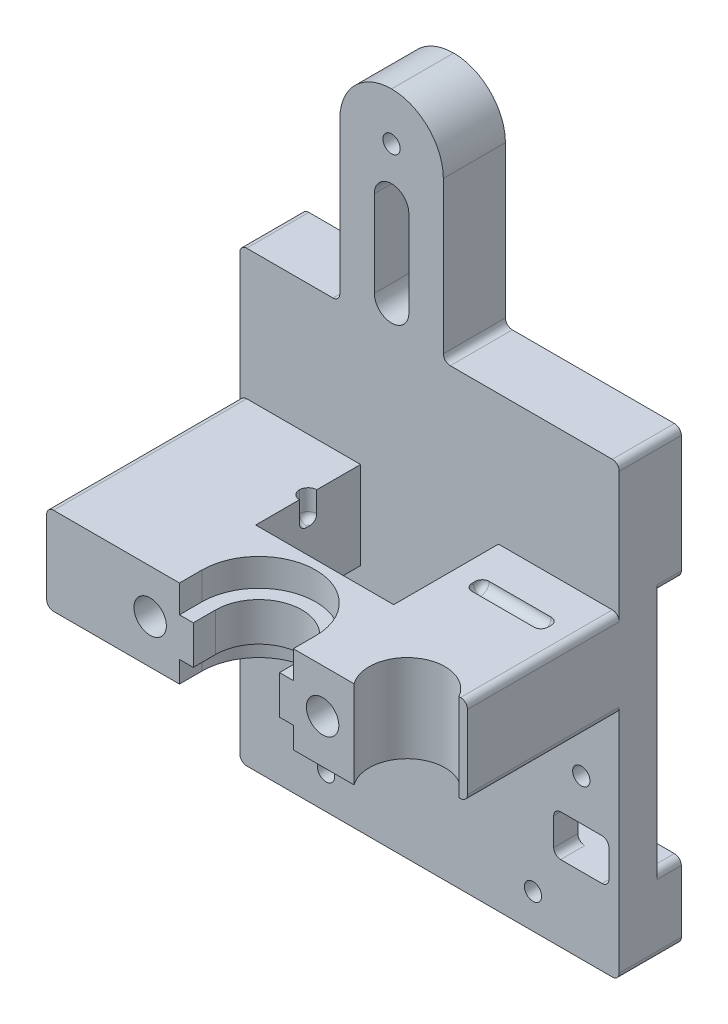
SolidWorks part; units mm, degrees
ref_plane "XY" through (0, 0, 0) normal (0, 0, 1) x (1, 0, 0)
ref_plane "XZ" through (0, 0, 0) normal (0, 1, 0) x (1, 0, 0)
ref_plane "YZ" through (0, 0, 0) normal (1, 0, 0) x (0, 0, -1)
sketch "Sketch1" plane through (0, 0, 0) normal (0, 0, 1) x (1, 0, 0)
  line L0 (-27.5, 17.25) -> (-13, 17.25)
  line L1 (27.5, 47.75) -> (2, 47.75) construction
  line L2 (27.5, 47.75) -> (27.5, 17.25) construction
  line L3 (27.5, -47.75) -> (-27.5, -47.75)
  line L4 (-27.5, 47.75) -> (-27.5, 17.25) construction
  line L5 (27.5, 47.75) -> (-27.5, -47.75) construction
  line L6 (27.5, -47.75) -> (-27.5, 47.75) construction
  line L7 (-13, 17.25) -> (-13, 47.75)
  line L8 (2, 47.75) -> (2, 17.25)
  line L9 (2, 17.25) -> (27.5, 17.25)
  line L10 (-27.5, 17.25) -> (-27.5, -47.75)
  line L11 (-13, 47.75) -> (-27.5, 47.75) construction
  line L12 (2, 47.75) -> (-13, 47.75)
  line L13 (27.5, 17.25) -> (27.5, -47.75)
  line L14 (-5.5, 33.35) -> (-5.5, 20.85) construction
  line L15 (-3, 33.35) -> (-3, 20.85)
  line L16 (-8, 33.35) -> (-8, 20.85)
  line L17 (0, 0) -> (0, -86.6792) construction
  line L18 (26, -30.75) -> (18, -30.75)
  line L19 (26, -30.75) -> (26, -36.75)
  line L20 (26, -36.75) -> (18, -36.75)
  line L21 (18, -30.75) -> (18, -36.75)
  line L22 (26, -30.75) -> (18, -36.75) construction
  line L23 (26, -36.75) -> (18, -30.75) construction
  arc A0 (-3, 33.35) -> (-8, 33.35) centre (-5.5, 33.35) ccw
  arc A1 (-8, 20.85) -> (-3, 20.85) centre (-5.5, 20.85) ccw
  circle A2 centre (-5.5, 40.85) radius 1.25
  circle A3 centre (-22, -24.75) radius 1.25
  circle A4 centre (-15, -42.75) radius 1.25
  circle A5 centre (15, -42.75) radius 1.25
  circle A6 centre (22, -24.75) radius 1.25
  point P0 (0, 0)
  point P14 (-5.5, 27.1)
  point P21 (22, -33.75)
  dimension "D6" = 2.5
  dimension "D10" = 2.5
  dimension "D16" = 2.5
  dimension "D1" = 55
  dimension "D2" = 95.5
  dimension "D3" = 14.5
  dimension "D4" = 25.5
  dimension "D5" = 30.5
  dimension "D7" = 12.5
  dimension "D8" = 7.5
  dimension "D9" = 20.65
  dimension "D11" = 6.9
  dimension "D12" = 8
  dimension "D13" = 6
  dimension "D14" = 5.5
  dimension "D15" = 14
  dimension "D17" = 5.5
  dimension "D18" = 12.5
  dimension "D19" = 5
  dimension "D20" = 23
extrude "Boss-Extrude1" add sketch "Sketch1" along normal blind 9
fillet "Fillet1" radius 7.5 2 edges at (-13, 47.75, 4.5) (2, 47.75, 4.5)
fillet "Fillet2" radius 1 6 edges at (-27.5, -47.75, 4.5) (-13, 17.25, 4.5) (-27.5, 17.25, 4.5) (2, 17.25, 4.5) (27.5, 17.25, 4.5) (27.5, -47.75, 4.5)
ref_plane "Plane1" through (0, -14.35, 0) normal (0, -1, 0) x (-1, 0, 0)
sketch "Sketch2" plane through (0, -14.35, 0) normal (0, -1, 0) x (-1, 0, 0)
  line L0 (-27.5, 0) -> (-27.5, -9) construction
  line L1 (27.5, -9) -> (10, -9)
  line L2 (27.5, -9) -> (27.5, -37)
  line L3 (27.5, -37) -> (6.25, -37)
  line L4 (-27.5, -9) -> (-27.5, -31)
  line L5 (-10, -9) -> (-27.5, -9)
  line L6 (-10, -24.2) -> (10, -24.2)
  line L7 (-10, -24.2) -> (-10, -9)
  line L8 (-27.5, -31) -> (-26.2631, -31)
  line L9 (10, -24.2) -> (10, -9)
  line L10 (-10, -24.2) -> (10, -9) construction
  line L11 (-10, -9) -> (10, -24.2) construction
  line L12 (-17.0629, -37) -> (-27.5, -37) construction
  line L13 (-27.5, -31) -> (-27.5, -37) construction
  line L14 (6.25, -33.75) -> (6.25, -37)
  line L15 (-6.25, -33.75) -> (-6.25, -37)
  line L16 (-6.25, -37) -> (-17.0629, -37)
  arc A0 (-26.2631, -31) -> (-17.0629, -37) centre (-21.5, -33.75) cw
  arc A1 (6.25, -33.75) -> (-6.25, -33.75) centre (0, -33.75) ccw
  point P7 (0, -16.6)
  dimension "D4" = 5.5
  dimension "D8" = 12.5
  dimension "D1" = 28
  dimension "D2" = 20
  dimension "D3" = 15.2
  dimension "D5" = 6
  dimension "D6" = 6
  dimension "D7" = 3.25
  dimension "D9" = 3.25
extrude "Boss-Extrude2" add sketch "Sketch2" against normal blind 12.7
sketch "Sketch3" plane through (0, 0, 37) normal (0, 0, 1) x (1, 0, 0)
  line L0 (-6.25, -1.65) -> (-8.25, -1.65)
  line L1 (-27.5, -1.65) -> (-10, -1.65) construction
  line L2 (-8.25, -1.65) -> (-8.25, -5.65)
  line L3 (-8.25, -5.65) -> (-6.25, -5.65)
  line L4 (-6.25, -1.65) -> (-6.25, -14.35) construction
  line L5 (-6.25, -5.65) -> (-6.25, -1.65)
  line L6 (-6.25, -14.35) -> (-6.25, -11.25)
  line L7 (-28.6032, -14.35) -> (28.6032, -14.35) construction
  line L8 (-6.25, -11.25) -> (-8.25, -11.25)
  line L9 (-8.25, -11.25) -> (-8.25, -14.35)
  line L10 (-8.25, -14.35) -> (-6.25, -14.35)
  line L11 (-27.5, -8) -> (8.666, -8) construction
  line L12 (-27.5, -1.65) -> (-27.5, -14.35) construction
  dimension "D1" = 4
  dimension "D2" = 2
  dimension "D3" = 3.1
sketch "Sketch4" plane through (0, -1.65, 0) normal (0, 1, 0) x (1, 0, 0)
  line L0 (-6.25, -33.75) -> (-6.25, -37) construction
  line L1 (6.25, -37) -> (6.25, -33.75) construction
  line L2 (-6.25, -33.75) -> (-6.25, -37)
  line L3 (6.25, -37) -> (6.25, -33.75)
  arc A0 (6.25, -33.75) -> (-6.25, -33.75) centre (0, -33.75) ccw construction
  arc A1 (6.25, -33.75) -> (-6.25, -33.75) centre (0, -33.75) ccw
sweep "Cut-Sweep1" cut profiles "Sketch3" path "Sketch4"
sketch "Sketch5" plane through (0, 0, 37) normal (0, 0, 1) x (1, 0, 0)
  line L0 (0, 0) -> (0, -23.2005) construction
  circle A0 centre (-12.5, -8) radius 1.75
  circle A1 centre (12.5, -8) radius 1.75
  dimension "D1" = 12.5
  dimension "D3" = 3.5
  dimension "D2" = 8
extrude "Cut-Extrude1" cut sketch "Sketch5" against normal blind 10
sketch "Sketch6" plane through (0, 0, 37) normal (0, 0, 1) x (1, 0, 0)
  circle A0 centre (-12.5, -8) radius 2.35
  circle A1 centre (12.5, -8) radius 2.35
  dimension "D1" = 4.7
extrude "Cut-Extrude2" cut sketch "Sketch6" against normal blind 5
sketch "Sketch7" plane through (-10, 0, 0) normal (1, 0, 0) x (0, 0, -1)
  line L0 (-9, -1.65) -> (-24.2, -1.65) construction
  line L1 (-17.85, -1.65) -> (-15.35, -1.65)
  line L2 (-17.85, -1.65) -> (-17.85, -5.65)
  line L3 (-17.85, -5.65) -> (-15.35, -5.65)
  line L4 (-15.35, -1.65) -> (-15.35, -5.65)
  dimension "D1" = 2.5
  dimension "D2" = 4
  dimension "D3" = 15.35
extrude "Cut-Extrude3" cut sketch "Sketch7" against normal blind 1.25
fillet "Fillet3" radius 1.25 2 edges at (-11.25, -3.65, 17.85) (-11.25, -3.65, 15.35)
fillet "Fillet4" radius 1 2 edges at (-10.8839, -5.65, 15.7161) (-10.8839, -5.65, 17.4839)
sketch "Sketch8" plane through (0, -1.65, 0) normal (0, 1, 0) x (1, 0, 0)
  line L1 (13, -14.35) -> (24, -14.35)
  line L2 (13, -14.35) -> (13, -16.85)
  line L3 (13, -16.85) -> (24, -16.85)
  line L4 (24, -14.35) -> (24, -16.85)
  dimension "D1" = 11
  dimension "D2" = 2.5
  dimension "D3" = 14.35
  dimension "D4" = 13
extrude "Cut-Extrude4" cut sketch "Sketch8" against normal blind 1.25
fillet "Fillet5" radius 1.25 2 edges at (18.5, -2.9, 16.85) (18.5, -2.9, 14.35)
fillet "Fillet6" radius 1 4 edges at (24, -2.5339, 16.4839) (13, -2.5339, 16.4839) (24, -2.5339, 14.7161) (13, -2.5339, 14.7161)
sketch "Sketch9" plane through (0, 0, 0) normal (0, 0, -1) x (-1, 0, 0)
  line L0 (0, 0) -> (0, -62.4758) construction
  circle A0 centre (0, -15.25) radius 2.35
  circle A1 centre (-12, -3.25) radius 1.5
  circle A2 centre (-12, -27.25) radius 1.5
  circle A3 centre (-22, -5.75) radius 1.25
  circle A4 centre (12, -27.25) radius 1.5
  circle A5 centre (12, -3.25) radius 1.5
  circle A6 centre (22, -5.75) radius 1.25
  dimension "D1" = 4.7
  dimension "D3" = 12
  dimension "D5" = 3
  dimension "D9" = 2.5
  dimension "D2" = 15.25
  dimension "D4" = 3.25
  dimension "D6" = 24
  dimension "D7" = 10
  dimension "D8" = 2.5
extrude "Cut-Extrude5" cut sketch "Sketch9" against normal blind 8 contours A1 | A2 | A5 | A4
extrude "Cut-Extrude6" cut sketch "Sketch9<3>" against normal blind 5 contours A0
sketch "Sketch9<3>" plane through (0, 0, 0) normal (0, 0, -1) x (-1, 0, 0) same geometry as "Sketch9"
extrude "Cut-Extrude7" cut sketch "Sketch9<4>" against normal blind 23 contours A3 | A6
sketch "Sketch9<4>" plane through (0, 0, 0) normal (0, 0, -1) x (-1, 0, 0) same geometry as "Sketch9"
sketch "Sketch10" plane through (0, 0, 0) normal (0, 0, -1) x (-1, 0, 0)
  circle A0 centre (0, -15.25) radius 1.5
  dimension "D1" = 3
extrude "Cut-Extrude8" cut sketch "Sketch10" against normal blind 8
sketch "Sketch11" plane through (0, 0, 0) normal (0, 0, -1) x (-1, 0, 0)
  line L0 (-27.5, -46.75) -> (-27.5, 16.25) construction
  line L1 (-27.5, -1.75) -> (-16.5, -1.75)
  line L2 (-27.5, -1.75) -> (-27.5, -36.75)
  line L3 (-27.5, -36.75) -> (-16.5, -36.75)
  line L4 (-16.5, -1.75) -> (-16.5, -36.75)
  dimension "D1" = 35
  dimension "D2" = 11
  dimension "D3" = 1.75
extrude "Cut-Extrude9" cut sketch "Sketch11" against normal blind 3.5
sketch "Sketch13" plane through (0, 0, 3.5) normal (0, 0, -1) x (-1, 0, 0)
  line L0 (-16.5, -36.75) -> (-16.5, -1.75) construction
  line L1 (-17.3, -9.25) -> (-26.7, -9.25)
  line L2 (-17.3, -9.25) -> (-17.3, -21.25)
  line L3 (-17.3, -21.25) -> (-26.7, -21.25)
  line L4 (-26.7, -9.25) -> (-26.7, -21.25)
  line L5 (-16.5, -1.75) -> (-27.5, -1.75) construction
  dimension "D1" = 0.8
  dimension "D2" = 9.4
  dimension "D3" = 12
  dimension "D4" = 7.5
extrude "Cut-Extrude10" cut sketch "Sketch13" against normal blind 1.5
mirror "Mirror1" about plane through (0, 0, 0) normal (1, 0, 0) of "Cut-Extrude10", "Cut-Extrude9"
sketch "Sketch12" plane through (16.5, 0, 0) normal (1, 0, 0) x (0, 0, -1)
  line L0 (-3.5, -36.75) -> (-3.5, -30.75) construction
  line L1 (-3.5, -36.75) -> (-3.5, -30.75) construction
  line L2 (-3.5, -30.75) -> (-2.5, -30.75)
  line L3 (-2.5, -30.75) -> (-2.5, -36.75)
  line L4 (-3.5, -36.75) -> (0, -36.75) construction
  line L5 (-2.5, -36.75) -> (-5.5, -36.75)
  line L6 (-5.5, -36.75) -> (-5.5, -30.75)
  line L7 (-5.5, -30.75) -> (-3.5, -30.75)
  line L8 (0, -36.75) -> (0, -1.75) construction
  dimension "D1" = 5.5
  dimension "D2" = 3
extrude "Cut-Extrude11" cut sketch "Sketch12" against normal up to surface (33 mm away) contours L6 L7 L2 L3 L5 up to face at (-16.5, -19.25, 1.75)
sketch "Sketch15" plane through (18, 0, 0) normal (1, 0, 0) x (0, 0, -1)
  line L0 (-3.5, -36.75) -> (-5.5, -36.75) construction
  line L1 (-5.5, -36.75) -> (-5.5, -30.75) construction
  line L2 (-5.5, -30.75) -> (-3.5, -30.75) construction
  line L3 (-3.5, -36.75) -> (-5.5, -36.75)
  line L4 (-5.5, -36.75) -> (-5.5, -30.75)
  line L5 (-5.5, -30.75) -> (-3.5, -30.75)
  line L6 (-3.5, -30.75) -> (-3.5, -36.75)
extrude "Cut-Extrude12" cut sketch "Sketch15" against normal up to surface (1.5 mm away) up to face at (16.5, -33.75, 4.5)
fillet "Fillet7" radius 1 8 edges at (18, -36.75, 7.25) (26, -36.75, 6.25) (26, -30.75, 6.25) (18, -30.75, 7.25) (27.5, -1.75, 1.75) (27.5, -36.75, 1.75) (-27.5, -1.75, 1.75) (-27.5, -36.75, 1.75)
sketch "Sketch16" plane through (0, 0, 0) normal (0, 0, -1) x (-1, 0, 0)
  line L0 (26.5, -36.75) -> (16.5, -36.75) construction
  line L1 (18, -36.75) -> (26, -36.75)
  line L2 (18, -36.75) -> (18, -30.75)
  line L3 (18, -30.75) -> (26, -30.75)
  line L4 (26, -36.75) -> (26, -30.75)
  dimension "D1" = 6
  dimension "D2" = 8
  dimension "D3" = 18
extrude "Cut-Extrude13" cut sketch "Sketch16" against normal blind 7.5
sketch "Sketch17" plane through (0, -36.75, 0) normal (0, 1, 0) x (1, 0, 0)
  line L0 (-18, -7.5) -> (-18, -3.5) construction
  line L1 (-18, -7.5) -> (-18, -3.5)
  line L2 (-18, -3.5) -> (-16.5, -3.5) construction
  line L3 (-16.5, -3.5) -> (-16.5, -5.5) construction
  line L4 (-18, -3.5) -> (-16.5, -3.5)
  line L5 (-16.5, -3.5) -> (-16.5, -5.5)
  line L6 (-16.5, -5.5) -> (-18, -7.5)
extrude "Cut-Extrude14" cut sketch "Sketch17" along normal up to surface (6 mm away) up to face at (-22, -30.75, 5.5)
fillet "Fillet8" radius 1 4 edges at (27.5, -14.35, 20) (-27.5, -14.35, 23) (27.5, -1.65, 20) (-27.5, -1.65, 23)
